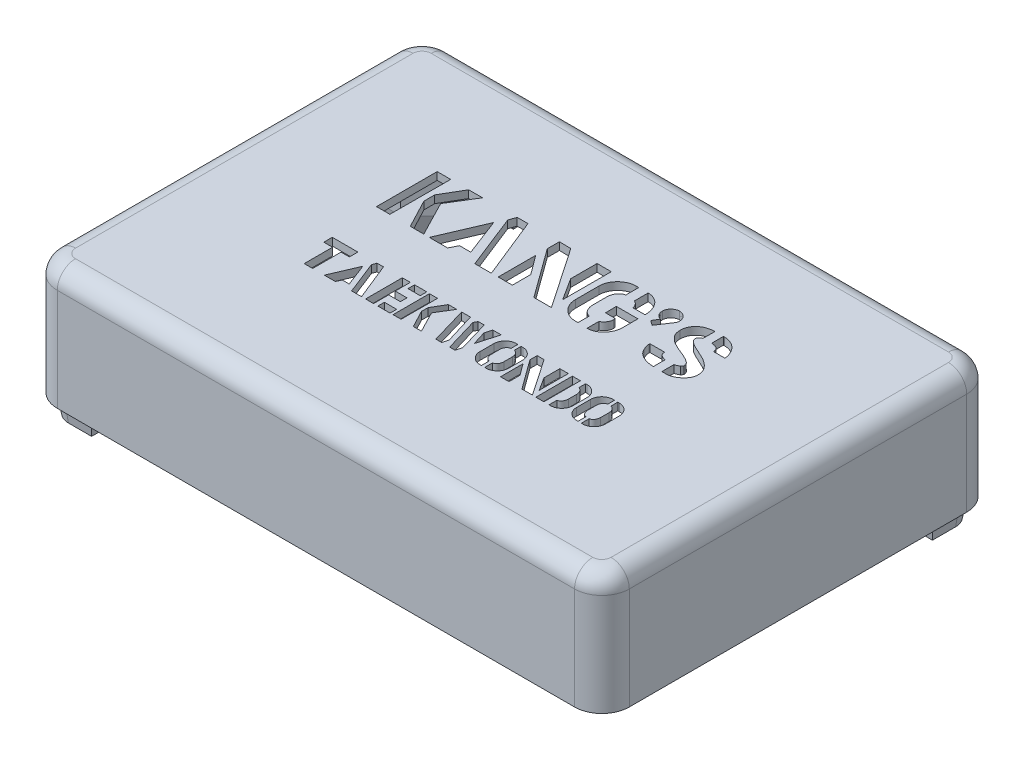
SolidWorks part; units mm, degrees
ref_plane "Front Plane" through (0, 0, 0) normal (0, 0, 1) x (1, 0, 0)
ref_plane "Top Plane" through (0, 0, 0) normal (0, 1, 0) x (1, 0, 0)
ref_plane "Right Plane" through (0, 0, 0) normal (1, 0, 0) x (0, 0, -1)
sketch "Sketch1" plane through (0, 0, 0) normal (0, 1, 0) x (1, 0, 0)
  line L0 (-41.5, -30.5958) -> (-41.5, 24.85)
  line L1 (-37, -33.5958) -> (48, -33.5958)
  line L2 (-40, -30.5958) -> (-40, 24.85)
  line L3 (-37, 27.85) -> (48, 27.85)
  line L4 (51, -30.5958) -> (51, 24.85)
  line L5 (-40, -33.5958) -> (51, 27.85) construction
  line L6 (-40, 27.85) -> (51, -33.5958) construction
  line L7 (-37, 29.35) -> (48, 29.35)
  line L8 (52.5, -30.5958) -> (52.5, 24.85)
  line L9 (-37, -35.0958) -> (48, -35.0958)
  line L12 (-37, 29.35) -> (48, 29.35) construction
  line L13 (48, -35.0958) -> (-37, -35.0958) construction
  line L14 (52.5, 24.85) -> (52.5, -30.5958) construction
  line L15 (-41.5, -30.5958) -> (-41.5, 24.85) construction
  arc A0 (48, -33.5958) -> (51, -30.5958) centre (48, -30.5958) ccw
  arc A1 (-37, -33.5958) -> (-40, -30.5958) centre (-37, -30.5958) cw
  arc A2 (-40, 24.85) -> (-37, 27.85) centre (-37, 24.85) cw
  arc A3 (48, 27.85) -> (51, 24.85) centre (48, 24.85) cw
  arc A4 (-41.5, 24.85) -> (-37, 29.35) centre (-37, 24.85) cw
  arc A5 (48, 29.35) -> (52.5, 24.85) centre (48, 24.85) cw
  arc A6 (48, -35.0958) -> (52.5, -30.5958) centre (48, -30.5958) ccw
  arc A7 (-37, -35.0958) -> (-41.5, -30.5958) centre (-37, -30.5958) cw
  point P30 (2.3511, -11.4424)
  point P32 (47.7082, -39.3059)
  dimension "D1" = 3
  dimension "D2" = 1.5
extrude "Boss-Extrude1" add sketch "Sketch1" along normal blind 1.25 contours A7 L9 A6 L8 A5 L7 A4 L0 L3 A3 L4 A0 L1 A1 L2 A2 | A3 L3 A2 L2 A1 L1 A0 L4 region at (-40.3603, 0, 2.8729) region at (5.5, 0, 2.8729)
extrude "Boss-Extrude2" add sketch "Sketch1<3>" against normal up to surface (18.5512 mm away)
sketch "Sketch1<3>" plane through (0, 0, 0) normal (0, 1, 0) x (1, 0, 0) same geometry as "Sketch1"
sketch "Sketch2" plane through (0, 0, -29.35) normal (0, 0, -1) x (-1, 0, 0)
  line L5 (25.025, -5.0212) -> (-19.705, -5.0212)
  line L6 (25.025, -5.0212) -> (25.025, -18.5512)
  line L7 (25.025, -18.5512) -> (-19.705, -18.5512)
  line L30 (-19.705, -5.0212) -> (-19.705, -18.5512)
  line L32 (-48, -18.5512) -> (37, -18.5512) construction
  line L34 (-40.025, -18.5512) -> (-25.775, -18.5512)
  line L35 (-40.025, -18.5512) -> (-40.025, -5.0212)
  line L36 (24.525, -6.0212) -> (11.275, -6.0212) construction
  line L38 (-40.025, -5.0212) -> (-25.775, -5.0212)
  line L39 (-25.775, -18.5512) -> (-25.775, -5.0212)
  dimension "D2" = 1
  dimension "D3" = 0.5
  dimension "D4" = 0.5
  dimension "D5" = 0.5
  dimension "D1" = 0.5
extrude "Cut-Extrude1" cut sketch "Sketch2" against normal up to next
sketch "Sketch3" plane through (0, 0, 0) normal (0, -1, 0) x (1, 0, 0)
  line L0 (-32.6645, -24.05) -> (-36.2, -20.5145)
  line L1 (-36.2, 26.2603) -> (-32.6645, 29.7958)
  line L2 (43.6645, -24.05) -> (47.2, -20.5145)
  line L3 (48, -28.05) -> (43.6645, -28.05)
  line L4 (43.6645, -28.05) -> (43.6645, -24.05)
  line L5 (51.2, -24.85) -> (51.2, -20.5145)
  line L6 (51.2, -20.5145) -> (47.2, -20.5145)
  line L7 (-37, -28.05) -> (-32.6645, -28.05)
  line L8 (-32.6645, -28.05) -> (-32.6645, -24.05)
  line L9 (-40.2, -24.85) -> (-40.2, -20.5145)
  line L10 (-40.2, -20.5145) -> (-36.2, -20.5145)
  line L11 (-40.2, 30.5958) -> (-40.2, 26.2603)
  line L12 (-40.2, 26.2603) -> (-36.2, 26.2603)
  line L13 (-32.6645, 29.7958) -> (-32.6645, 33.7958)
  line L14 (-32.6645, 33.7958) -> (-37, 33.7958)
  arc A0 (51.2, -24.85) -> (48, -28.05) centre (48, -24.85) cw
  arc A1 (48, -27.85) -> (51, -24.85) centre (48, -24.85) ccw construction
  arc A3 (-37, -28.05) -> (-40.2, -24.85) centre (-37, -24.85) cw
  arc A4 (-40, -24.85) -> (-37, -27.85) centre (-37, -24.85) ccw construction
  arc A5 (-40.2, 30.5958) -> (-37, 33.7958) centre (-37, 30.5958) cw
  arc A6 (-37, 33.5958) -> (-40, 30.5958) centre (-37, 30.5958) ccw construction
  dimension "D1" = 0.2
  dimension "D2" = 5
  dimension "D3" = 4
extrude "Boss-Extrude3" add sketch "Sketch3" along normal up to surface (18.5512 mm away) up to face at (5.9, -18.5512, -3.4217)
extrude "Boss-Extrude4" add sketch "Sketch3<3>" along normal blind 3 draft 10 from surface starting at face at (22.74, -18.5512, -28.6)
sketch "Sketch3<3>" plane through (0, 0, 0) normal (0, -1, 0) x (1, 0, 0) same geometry as "Sketch3"
fillet "Fillet1" radius 3 22 edges at (-40.182, 1.25, -28.032) (-41.5, 1.25, 2.8729) (-40.182, 1.25, 33.7778) (5.5, 1.25, 35.0958) (51.182, 1.25, 33.7778) (52.5, 1.25, 2.8729) (51.182, 1.25, -28.032) (5.5, 1.25, -29.35) (-40, 0, 2.8729) (5.5, 0, -27.85) (51, 0, 5.0407) (50.1213, 0, 32.7171) (7.6678, 0, 33.5958) (-32.6645, 0, -25.95) (-34.4322, 0, -22.2822) (-38.1, 0, -20.5145) (-38.1, 0, 26.2603) (-34.4322, 0, 28.028) (-32.6645, 0, 31.6958) (49.1, 0, -20.5145) (45.4322, 0, -22.2822) (43.6645, 0, -25.95)
sketch "Sketch4" plane through (0, -18.5512, 0) normal (0, -1, 0) x (1, 0, 0)
  line L0 (48, -29.35) -> (40.025, -29.35) construction
  line L1 (37.6139, -29.35) -> (46.45, -29.35)
  line L2 (37.6139, -29.35) -> (37.6139, -21.2645)
  line L3 (37.6139, -21.2645) -> (46.45, -21.2645)
  line L4 (46.45, -29.35) -> (46.45, -21.2645)
  line L6 (47.2, -20.5145) -> (43.6645, -24.05) construction
  line L10 (45.95, -27.85) -> (45.95, -17.0042) construction
  point P6 (46.3057, -21.4087)
  point P8 (37.6139, -36.4297)
  dimension "D1" = 0.5
extrude "Cut-Extrude2" cut sketch "Sketch4" along normal through all
sketch "Sketch5" plane through (0, 1.25, 0) normal (0, 1, 0) x (1, 0, 0)
  line L0 (-38.5, 0) -> (49.5, 0) construction
  line L1 (-38.5, -14) -> (49.5, -14) construction
  line L2 (-38.5, 24.85) -> (-38.5, -30.5958) construction
  line L3 (49.5, -30.5958) -> (49.5, 24.85) construction
  text T0 "KANG'S" font "Stencil Gothic" height 10
  text T1 "TAEKWONDO" font "Stencil Gothic" height 6
  dimension "D1" = 14
extrude "Cut-Extrude3" cut sketch "Sketch5" against normal through all
